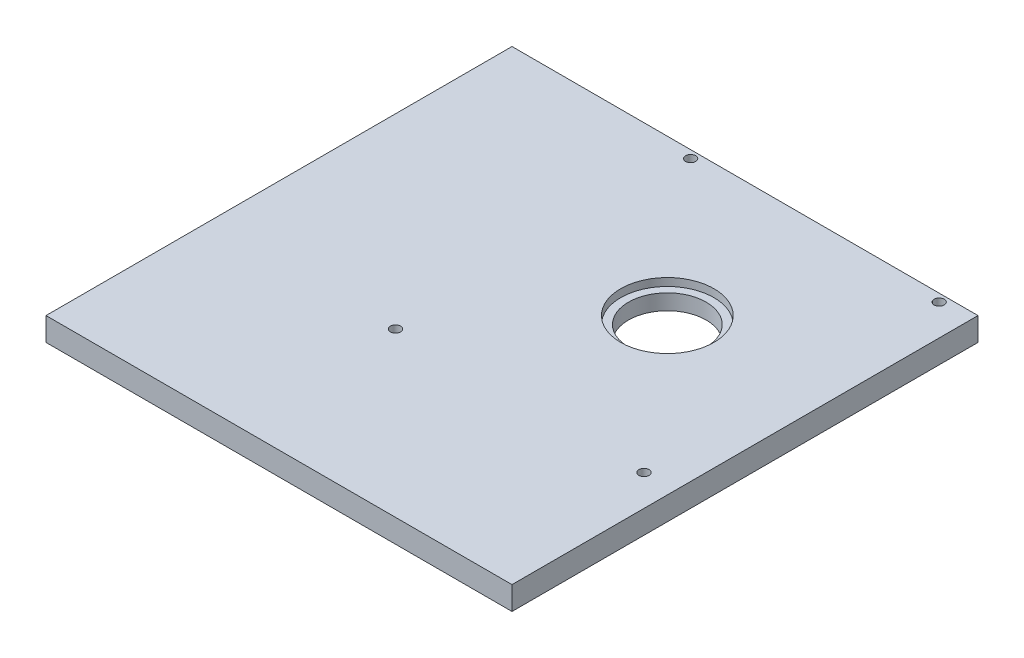
SolidWorks part; units mm, degrees
ref_plane "Front Plane" through (0, 0, 0) normal (0, 0, 1) x (1, 0, 0)
ref_plane "Top Plane" through (0, 0, 0) normal (0, 1, 0) x (1, 0, 0)
ref_plane "Right Plane" through (0, 0, 0) normal (1, 0, 0) x (0, 0, -1)
sketch "MountingHoles" plane through (0, 0, 0) normal (0, 1, 0) x (1, 0, 0)
  circle A0 centre (-80, 95) radius 3.25
  circle A1 centre (-80, -95) radius 3.25
  circle A2 centre (80, -95) radius 3.25
  circle A3 centre (80, 95) radius 3.25
  dimension "D1" = 6.5
  dimension "D2" = 190
  dimension "D3" = 160
  dimension "D4" = 80
  dimension "D5" = 95
sketch "BaseSketch" plane through (0, 0, 0) normal (0, 1, 0) x (1, 0, 0)
  line L1 (-200, 100) -> (100, 100)
  line L2 (-200, 100) -> (-200, -200)
  line L3 (-200, -200) -> (100, -200)
  line L4 (100, 100) -> (100, -200)
  dimension "D1" = 300
  dimension "D2" = 300
  dimension "D3" = 100
  dimension "D4" = 100
extrude "Base" add sketch "BaseSketch" along normal blind 15
extrude "Cut-Extrude1" cut sketch "MountingHoles" along normal up to surface (15 mm away) up to face at (-50, 15, 50)
sketch "BearingJ1" plane through (0, 0, 0) normal (0, 1, 0) x (1, 0, 0)
  circle A0 centre (0, 0) radius 25
  dimension "D1" = 50
extrude "Cut-Extrude3" cut sketch "BearingJ1" along direction (0, 1, 0) on the side of the normal up to next (15 mm away) contours A0
sketch "Sketch4" plane through (0, 15, 0) normal (0, 1, 0) x (1, 0, 0)
  line L1 (-62.5, -100) -> (62.5, -100) construction
  line L2 (-62.5, -100) -> (-62.5, 100) construction
  line L3 (-62.5, 100) -> (62.5, 100) construction
  line L4 (62.5, -100) -> (62.5, 100) construction
  line L5 (-62.5, -100) -> (62.5, 100) construction
  line L6 (-62.5, 100) -> (62.5, -100) construction
  circle A0 centre (0, 0) radius 75 construction
  point P7 (0, 0)
  dimension "D1" = 150
  dimension "D2" = 125
  dimension "D3" = 200
sketch "Sketch7" plane through (0, 15, 0) normal (0, 1, 0) x (1, 0, 0)
  line L0 (-62.5, -100) -> (-62.5, 100) construction
  line L1 (-62.5, 100) -> (62.5, 100) construction
  line L2 (-62.5, 80) -> (-62.5, 5) construction
  line L3 (0, 138.2666) -> (0, -138.2666) construction
  circle A0 centre (-62.5, 80) radius 3.5
  circle A1 centre (-62.5, 5) radius 3.5
  circle A2 centre (-62.5, -70) radius 3.5
  circle A3 centre (62.5, -70) radius 3.5
  circle A4 centre (62.5, 5) radius 3.5
  circle A5 centre (62.5, 80) radius 3.5
  point P14 (0, 0)
  dimension "D1" = 7
  dimension "D2" = 20
  dimension "D4" = 75
  dimension "D3" = 3
sketch "BearingRadialConstraint" plane through (0, 0, 0) normal (0, 1, 0) x (1, 0, 0)
  circle A0 centre (0, 0) radius 30
  dimension "D1" = 60
extrude "Cut-Extrude4" cut sketch "BearingRadialConstraint" against normal blind 5 from surface starting at face at (0, 15, 25)
